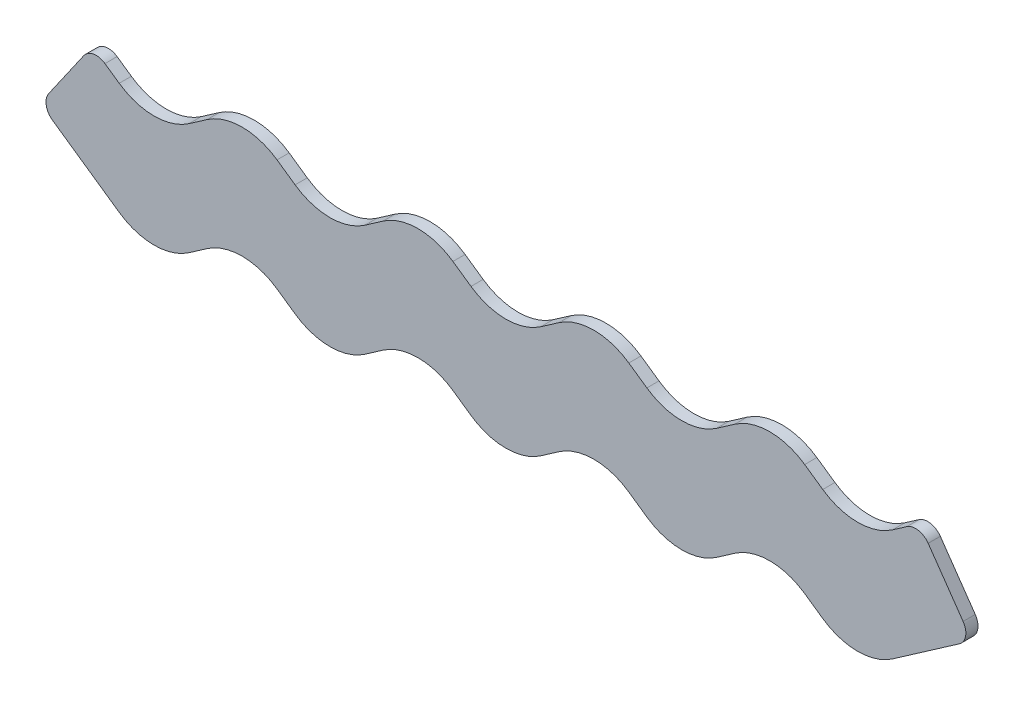
SolidWorks part; units mm, degrees
material "3003-H14"
ref_plane "X-Y Datum" through (0, 0, 0) normal (0, 0, 1) x (1, 0, 0)
ref_plane "X-Z Datum" through (0, 0, 0) normal (0, 1, 0) x (1, 0, 0)
ref_plane "Y-Z Datum" through (0, 0, 0) normal (1, 0, 0) x (0, 0, -1)
sketch "Sketch3" plane through (0, 0, 0) normal (0, 0, 1) x (1, 0, 0)
  line L0 (10.775, 10.775) -> (22.275, 34.775) construction
  line L1 (0, 0) -> (156.4633, 0) construction
  line L2 (0, 0) -> (0, 56.3098) construction
  line L3 (0, 56.3098) -> (156.4633, 56.3098) construction
  line L4 (156.4633, 0) -> (156.4633, 56.3098) construction
  line L5 (33.775, 10.775) -> (45.275, 34.775) construction
  line L6 (56.775, 10.775) -> (68.275, 34.775) construction
  line L7 (16.525, 22.775) -> (62.525, 22.775) construction
  line L8 (33.775, 10.775) -> (22.275, 34.775) construction
  line L9 (45.275, 34.775) -> (56.775, 10.775) construction
  line L10 (10.775, 10.775) -> (33.775, 10.775) construction
  line L11 (56.775, 10.775) -> (33.775, 10.775) construction
  line L12 (22.275, 34.775) -> (45.275, 34.775) construction
  line L13 (68.275, 34.775) -> (45.275, 34.775) construction
  line L14 (22.275, 34.775) -> (22.275, 10.775) construction
  line L15 (45.275, 10.775) -> (45.275, 34.775) construction
  line L16 (33.775, 10.775) -> (33.775, 34.775) construction
  line L17 (56.775, 34.775) -> (56.775, 10.775)
  line L18 (16.525, 22.775) -> (22.275, 18.775)
  line L19 (45.275, 34.775) -> (36.4297, 28.6218)
  line L20 (33.775, 10.775) -> (42.6203, 16.9282)
  line L21 (45.275, 18.775) -> (33.775, 26.775)
  line L22 (16.525, 22.775) -> (10.775, 26.775)
  line L23 (45.275, 34.775) -> (54.1203, 28.6218)
  line L24 (51.025, 22.775) -> (56.775, 26.775)
  line L25 (62.525, 22.775) -> (68.275, 18.775)
  line L26 (24.9297, 16.9282) -> (33.775, 10.775)
  line L27 (33.775, 26.775) -> (22.275, 18.775)
  line L28 (45.275, 18.775) -> (51.025, 22.775)
  line L29 (56.775, 26.775) -> (62.525, 22.775)
  line L30 (65.9514, 27.7004) -> (71.7014, 23.7004)
  line L31 (56.775, 34.084) -> (65.9514, 27.7004)
  line L32 (47.5986, 27.7004) -> (56.775, 34.084)
  line L33 (45.275, 26.084) -> (47.5986, 27.7004)
  line L34 (45.275, 26.084) -> (33.775, 34.084)
  line L35 (33.775, 34.084) -> (22.275, 26.084)
  line L36 (19.9514, 27.7004) -> (22.275, 26.084)
  line L37 (19.9514, 27.7004) -> (14.2014, 31.7004)
  line L38 (13.0986, 17.8496) -> (7.3486, 21.8496)
  line L39 (13.0986, 17.8496) -> (22.275, 11.466)
  line L40 (33.775, 19.466) -> (22.275, 11.466)
  line L41 (45.275, 11.466) -> (33.775, 19.466)
  line L42 (45.275, 11.466) -> (54.4514, 17.8496)
  line L43 (54.4514, 17.8496) -> (56.775, 19.466)
  line L44 (56.775, 19.466) -> (59.0986, 17.8496)
  line L45 (59.0986, 17.8496) -> (64.8486, 13.8496)
  line L46 (64.8486, 13.8496) -> (71.7014, 23.7004)
  line L47 (7.3486, 21.8496) -> (14.2014, 31.7004)
  line L48 (56.775, 10.775) -> (68.275, 10.775) construction
  line L49 (68.275, 10.775) -> (68.275, 34.775)
  circle A0 centre (10.775, 10.775) radius 10.775 construction
  circle A1 centre (33.775, 10.775) radius 10.775 construction
  circle A2 centre (22.275, 34.775) radius 10.775 construction
  circle A3 centre (45.275, 34.775) radius 10.775 construction
  circle A4 centre (68.275, 34.775) radius 10.775 construction
  circle A5 centre (56.775, 10.775) radius 10.775 construction
  circle A6 centre (10.775, 10.775) radius 4.7 construction
  circle A7 centre (33.775, 10.775) radius 4.7 construction
  circle A8 centre (56.775, 10.775) radius 4.7 construction
  circle A9 centre (68.275, 34.775) radius 4.7 construction
  circle A10 centre (45.275, 34.775) radius 4.7 construction
  circle A11 centre (22.275, 34.775) radius 4.7 construction
  circle A18 centre (125.775, 10.775) radius 10.775 construction
  circle A19 centre (102.775, 10.775) radius 10.775 construction
  circle A20 centre (79.775, 10.775) radius 10.775 construction
  circle A21 centre (91.275, 34.775) radius 10.775 construction
  circle A22 centre (114.275, 34.775) radius 10.775 construction
  circle A23 centre (137.275, 34.775) radius 10.775 construction
  dimension "D1" = 21.55
  dimension "D9" = 9.4
  dimension "D2" = 23
  dimension "D3" = 24
  dimension "D4" = 11.5
  dimension "D6" = 23
  dimension "D8" = 23
  dimension "D10" = 6
  dimension "D11" = 6
  dimension "D5" = 6
  dimension "D7" = 5
extrude "Boss-Extrude1" add sketch "Sketch3" along normal blind 1.5875 contours L47 L22 L18 L27 L21 L28 L24 L17 L32 L33 L34 L35 L36 L37 | L47 L38 L39 L40 L41 L42 L43 L17 L24 L28 L21 L27 L18 L22 | L45 L46 L25 L29 L17 L44 | L25 L46 L30 L31 L17 L29 | L49 L46 L30 region at (62.525, 26.4295, 0) region at (34.6206, 26.2584, 0) region at (61.7184, 19.8949, 0) region at (32.9082, 19.2489, 0) region at (69.4171, 22.8531, 0)
ref_plane "Plane1" through (68.275, 0, 0) normal (1, 0, 0) x (0, 0, -1)
mirror "Mirror1" about plane through (68.275, 0, 0) normal (1, 0, 0) of "Boss-Extrude1"
sketch "Sketch4" plane through (0, 0, 1.5875) normal (0, 0, 1) x (1, 0, 0)
  line L0 (64.8486, 13.8496) -> (68.275, 11.466)
  line L1 (68.275, 11.466) -> (71.7014, 13.8496)
  line L24 (45.275, 11.466) -> (56.775, 19.466)
  line L25 (56.775, 19.466) -> (64.8486, 13.8496)
  line L26 (64.8486, 13.8496) -> (68.275, 18.775)
  line L29 (68.275, 18.775) -> (71.7014, 13.8496)
  line L31 (68.275, 18.775) -> (71.7014, 13.8496)
  line L33 (71.7014, 13.8496) -> (79.775, 19.466)
  line L35 (71.7014, 13.8496) -> (79.775, 19.466)
  line L37 (79.775, 19.466) -> (91.275, 11.466)
  line L39 (68.275, 26.084) -> (56.775, 34.084)
  line L40 (56.775, 34.084) -> (45.275, 26.084)
  line L41 (45.275, 26.084) -> (33.775, 34.084)
  line L42 (33.775, 34.084) -> (22.275, 26.084)
  line L43 (22.275, 26.084) -> (14.2014, 31.7004)
  line L44 (14.2014, 31.7004) -> (7.3486, 21.8496)
  line L45 (7.3486, 21.8496) -> (22.275, 11.466)
  line L46 (22.275, 11.466) -> (33.775, 19.466)
  line L47 (33.775, 19.466) -> (45.275, 11.466)
  line L48 (45.275, 11.466) -> (56.775, 19.466)
  line L49 (56.775, 19.466) -> (64.8486, 13.8496)
  line L50 (64.8486, 13.8496) -> (68.275, 18.775)
  line L63 (68.275, 26.084) -> (56.775, 34.084)
  line L64 (56.775, 34.084) -> (45.275, 26.084)
  line L65 (45.275, 26.084) -> (33.775, 34.084)
  line L66 (33.775, 34.084) -> (22.275, 26.084)
  line L67 (22.275, 26.084) -> (14.2014, 31.7004)
  line L68 (14.2014, 31.7004) -> (7.3486, 21.8496)
  line L69 (7.3486, 21.8496) -> (22.275, 11.466)
  line L70 (22.275, 11.466) -> (33.775, 19.466)
  line L71 (33.775, 19.466) -> (45.275, 11.466)
  line L72 (79.775, 19.466) -> (91.275, 11.466)
  line L73 (91.275, 11.466) -> (102.775, 19.466)
  line L74 (91.275, 11.466) -> (102.775, 19.466)
  line L75 (102.775, 19.466) -> (114.275, 11.466)
  line L76 (102.775, 19.466) -> (114.275, 11.466)
  line L77 (114.275, 11.466) -> (129.2014, 21.8496)
  line L78 (114.275, 11.466) -> (129.2014, 21.8496)
  line L79 (129.2014, 21.8496) -> (122.3486, 31.7004)
  line L80 (129.2014, 21.8496) -> (122.3486, 31.7004)
  line L81 (122.3486, 31.7004) -> (114.275, 26.084)
  line L82 (122.3486, 31.7004) -> (114.275, 26.084)
  line L83 (114.275, 26.084) -> (102.775, 34.084)
  line L84 (114.275, 26.084) -> (102.775, 34.084)
  line L85 (102.775, 34.084) -> (91.275, 26.084)
  line L86 (102.775, 34.084) -> (91.275, 26.084)
  line L87 (91.275, 26.084) -> (79.775, 34.084)
  line L88 (91.275, 26.084) -> (79.775, 34.084)
  line L89 (79.775, 34.084) -> (68.275, 26.084)
  line L90 (79.775, 34.084) -> (68.275, 26.084)
  point P2 (71.7014, 13.5217)
  line M27 (64.8486, 13.8496) -> (68.275, 18.775)
  line M28 (68.275, 18.775) -> (71.7014, 13.8496)
  dimension "D1" = 0
extrude "Boss-Extrude2" add sketch "Sketch4" against normal up to surface (1.5875 mm away) contours L0 L1 M28 M27 region at (68.275, 14.6969, 1.5875) up to face at (68.275, 22.6691, 0)
fillet "Fillet1" [suppressed] radius 2
fillet "Fillet2" radius 2 4 edges at (129.2014, 21.8496, 0.7937) (122.3486, 31.7004, 0.7937) (7.3486, 21.8496, 0.7937) (14.2014, 31.7004, 0.7937)
fillet "Fillet3" [suppressed] radius 8
fillet "Fillet4" [suppressed] radius 8
fillet "Fillet5" radius 8 18 edges at (22.275, 26.084, 0.7937) (22.275, 11.466, 0.7937) (33.775, 34.084, 0.7937) (33.775, 19.466, 0.7937) (45.275, 11.466, 0.7937) (45.275, 26.084, 0.7937) (56.775, 34.084, 0.7937) (56.775, 19.466, 0.7937) (68.275, 11.466, 0.7937) (68.275, 26.084, 0.7937) (79.775, 34.084, 0.7937) (79.775, 19.466, 0.7937) (91.275, 26.084, 0.7937) (91.275, 11.466, 0.7937) (102.775, 19.466, 0.7937) (114.275, 26.084, 0.7937) (114.275, 11.466, 0.7937) (102.775, 34.084, 0.7937)
